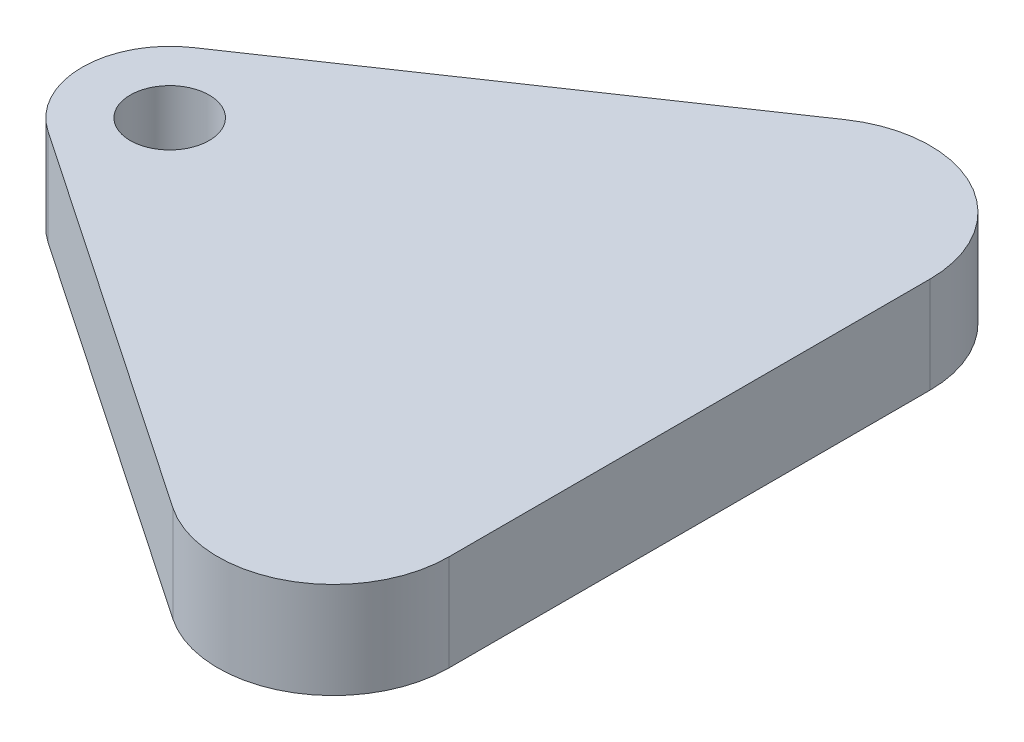
SolidWorks part; units mm, degrees
ref_plane "正面" through (0, 0, 0) normal (0, 0, 1) x (1, 0, 0)
ref_plane "平面" through (0, 0, 0) normal (0, 1, 0) x (1, 0, 0)
ref_plane "右側面" through (0, 0, 0) normal (1, 0, 0) x (0, 0, -1)
sketch "ｽｹｯﾁ1" plane through (0, 0, 0) normal (0, 1, 0) x (1, 0, 0)
  line L0 (-47.1103, 7.5296) -> (-6.7388, 34.9292)
  line L1 (12, 25) -> (12, -25)
  line L2 (-6.7388, -34.9292) -> (-47.1103, -7.5296)
  circle A2 centre (-42, 0) radius 4.1
  arc A3 (12, 25) -> (-6.7388, 34.9292) centre (0, 25) ccw
  arc A4 (-6.7388, -34.9292) -> (12, -25) centre (0, -25) ccw
  arc A5 (-47.1103, 7.5296) -> (-47.1103, -7.5296) centre (-42, 0) ccw
  point P1 (0, 0)
  point P16 (-4.1533, -32.5803)
  point P17 (0, 0)
  point P18 (0, 0)
  point P19 (0, 0)
  dimension "D1" = 8.2
  dimension "D2" = 12
  dimension "D5" = 42
  dimension "D6" = 25
  dimension "D8" = 5
  dimension "D4" = 12
  dimension "D3" = 25
extrude "ﾎﾞｽ - 押し出し1" add sketch "ｽｹｯﾁ1" along normal blind 10
sketch "ｽｹｯﾁ2" plane through (0, 0, 0) normal (0, -1, 0) x (1, 0, 0)
  line L1 (-5.1, 19.9) -> (5.1, 19.9)
  line L2 (-5.1, 19.9) -> (-5.1, 30.1)
  line L3 (-5.1, 30.1) -> (5.1, 30.1)
  line L4 (5.1, 19.9) -> (5.1, 30.1)
  line L5 (-5.1, 19.9) -> (5.1, 30.1) construction
  line L6 (-5.1, 30.1) -> (5.1, 19.9) construction
  line L7 (-5.1, -19.9) -> (5.1, -19.9)
  line L8 (-5.1, -19.9) -> (-5.1, -30.1)
  line L9 (-5.1, -30.1) -> (5.1, -30.1)
  line L10 (5.1, -19.9) -> (5.1, -30.1)
  line L11 (-5.1, -19.9) -> (5.1, -30.1) construction
  line L12 (-5.1, -30.1) -> (5.1, -19.9) construction
  point P0 (0, 25)
  point P5 (0, -25)
  point P10 (0, 0)
  dimension "D1" = 10.2
  dimension "D2" = 25
  dimension "D3" = 25
extrude "ｶｯﾄ - 押し出し1" cut sketch "ｽｹｯﾁ2" against normal blind 5
